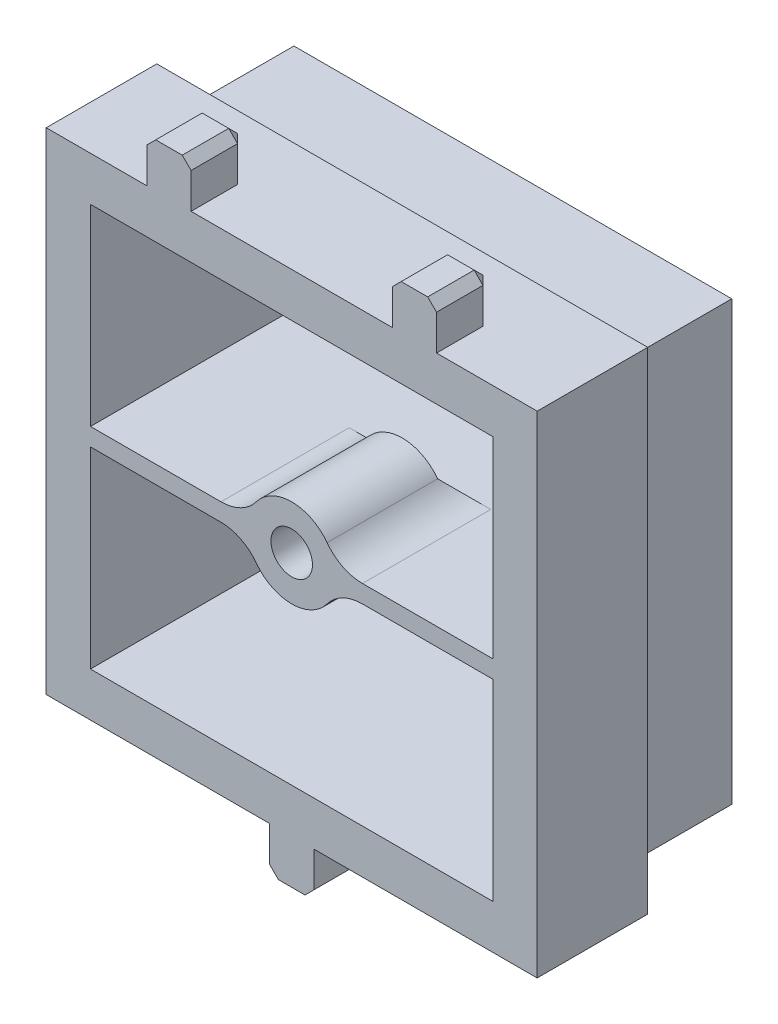
SolidWorks part; units mm, degrees
material "Nylon 101"
ref_plane "Front Plane" through (0, 0, 0) normal (0, 0, 1) x (1, 0, 0)
ref_plane "Top Plane" through (0, 0, 0) normal (0, 1, 0) x (1, 0, 0)
ref_plane "Right Plane" through (0, 0, 0) normal (1, 0, 0) x (0, 0, -1)
sketch "Sketch1" plane through (0, 0, 0) normal (0, 0, 1) x (1, 0, 0)
  line L0 (-6.4135, -106.3625) -> (-18.9865, -106.3625)
  line L4 (-6.4135, -100.076) -> (-18.9865, -100.076)
  line L5 (-18.9865, -100.076) -> (-18.9865, -112.649)
  line L6 (-18.9865, -112.649) -> (-6.4135, -112.649)
  line L7 (-6.4135, -112.649) -> (-6.4135, -100.076)
  line L8 (-6.4135, -100.076) -> (-18.9865, -100.076)
  line L9 (-18.9865, -100.076) -> (-18.9865, -112.649)
  line L10 (-18.9865, -112.649) -> (-6.4135, -112.649)
  line L11 (-6.4135, -112.649) -> (-6.4135, -100.076)
  dimension "D1" = 0
extrude "Extrude-Thin1" add sketch "Sketch1" along normal blind 6.35 thin contours L11 L8 L9 L10 thin type one direction reverse wall 0.508
extrude "Extrude-Thin2" add sketch "Sketch1<4>" along normal through all thin contours L0 thin type mid plane wall 0.508
sketch "Sketch1<4>" plane through (0, 0, 0) normal (0, 0, 1) x (1, 0, 0) same geometry as "Sketch1"
sketch "Sketch2" plane through (0, 0, 6.35) normal (0, 0, 1) x (1, 0, 0)
  line L0 (-18.9865, -100.076) -> (-18.9865, -112.649) construction
  line L1 (-18.9865, -112.649) -> (-6.4135, -112.649) construction
  line L2 (-6.4135, -112.649) -> (-6.4135, -100.076) construction
  line L3 (-6.4135, -100.076) -> (-18.9865, -100.076) construction
  line L8 (-18.9865, -100.076) -> (-18.9865, -112.649)
  line L9 (-18.9865, -112.649) -> (-6.4135, -112.649)
  line L10 (-6.4135, -112.649) -> (-6.4135, -100.076)
  line L11 (-6.4135, -100.076) -> (-18.9865, -100.076)
  line L12 (-19.7485, -113.411) -> (-5.6515, -113.411)
  line L13 (-5.6515, -113.411) -> (-5.6515, -99.314)
  line L14 (-5.6515, -99.314) -> (-19.7485, -99.314)
  line L15 (-19.7485, -99.314) -> (-19.7485, -113.411)
  dimension "D1" = 0.762
  dimension "D2" = 0.762
  dimension "D3" = 0.762
  dimension "D4" = 0.762
extrude "Boss-Extrude1" add sketch "Sketch2" against normal blind 3.175
sketch "Sketch3" plane through (0, 0, 6.35) normal (0, 0, 1) x (1, 0, 0)
  line L0 (-12.7, -106.6165) -> (-12.7, -106.1085) construction
  line L1 (-6.9215, -106.6165) -> (-18.4785, -106.6165) construction
  line L2 (-6.9215, -106.1085) -> (-18.4785, -106.1085) construction
  circle A0 centre (-12.7, -106.3625) radius 1.27
  dimension "D1" = 2.54
extrude "Boss-Extrude2" add sketch "Sketch3" against normal blind 3.175
fillet "Fillet2" radius 1.27 4 edges at (-13.9443, -106.1085, 4.7625) (-13.9443, -106.6165, 4.7625) (-11.4557, -106.6165, 4.7625) (-11.4557, -106.1085, 4.7625)
chamfer "Chamfer1" distance 0.508 angle 45 2 edges at (-12.7, -106.6165, 3.175) (-12.7, -106.1085, 3.175)
hole_wizard "#0-80 Tapped Hole1" positions "Sketch5" profile "Sketch4" tap size "#0-80" standard "ANSI Inch"
sketch "Sketch5" plane through (0, 0, 6.35) normal (0, 0, 1) x (1, 0, 0)
  point P0 (-12.7, -106.3625)
sketch "Sketch4" plane through (-12.7, -106.3625, 6.35) normal (1, 0, 0) x (0, -1, 0)
  line L0 (0, 0) -> (0, 3.6599)
  line L1 (0, 3.6599) -> (0.5956, 3.302)
  line L2 (0.5956, 3.302) -> (0.5956, 0)
  line L5 (0.5956, 0) -> (0, 0)
  line L10 (0, 3.6599) -> (-0.5956, 3.302) construction
  line L11 (0, -6.35) -> (0, 107.95) construction
  dimension "Tap Drill Dia." = 1.1913
  dimension "Tap Drill Depth" = 3.302
  dimension "Drill Angle" = 118
cosmetic thread "Hole Thread1" parameters "D1"=3.302, "D2"=1.524
sketch "Sketch6" plane through (0, 0, 6.35) normal (0, 0, 1) x (1, 0, 0)
  line L0 (-12.7, -113.411) -> (-12.7, -114.681)
  line L1 (-19.7485, -113.411) -> (-5.6515, -113.411) construction
  line L2 (-5.6515, -99.314) -> (-12.7, -99.314) construction
  line L3 (-5.6515, -99.314) -> (-19.7485, -99.314) construction
  line L4 (-12.7, -99.314) -> (-19.7485, -99.314) construction
  line L5 (-9.1757, -99.314) -> (-9.1757, -98.044)
  line L6 (-16.2242, -99.314) -> (-16.2242, -98.044)
  dimension "D1" = 1.27
  dimension "D2" = 1.27
extrude "Extrude-Thin3" add sketch "Sketch6" against normal blind 1.5875 thin thin type mid plane wall 1.27
chamfer "Chamfer2" distance 0.254 angle 45 15 edges at (-12.065, -114.046, 4.7625) (-12.7, -114.681, 4.7625) (-13.335, -114.046, 4.7625) (-8.5407, -98.044, 5.5562) (-9.8107, -98.044, 5.5562) (-16.8592, -98.044, 5.5562) (-15.5892, -98.044, 5.5562) (-13.335, -114.681, 5.5562) (-12.065, -114.681, 5.5562) (-9.8107, -98.679, 4.7625) (-8.5407, -98.679, 4.7625) (-9.1757, -98.044, 4.7625) (-16.8592, -98.679, 4.7625) (-16.2242, -98.044, 4.7625) (-15.5892, -98.679, 4.7625)
equation "\"D2@Sketch6\"=\"D1@Sketch6\""
